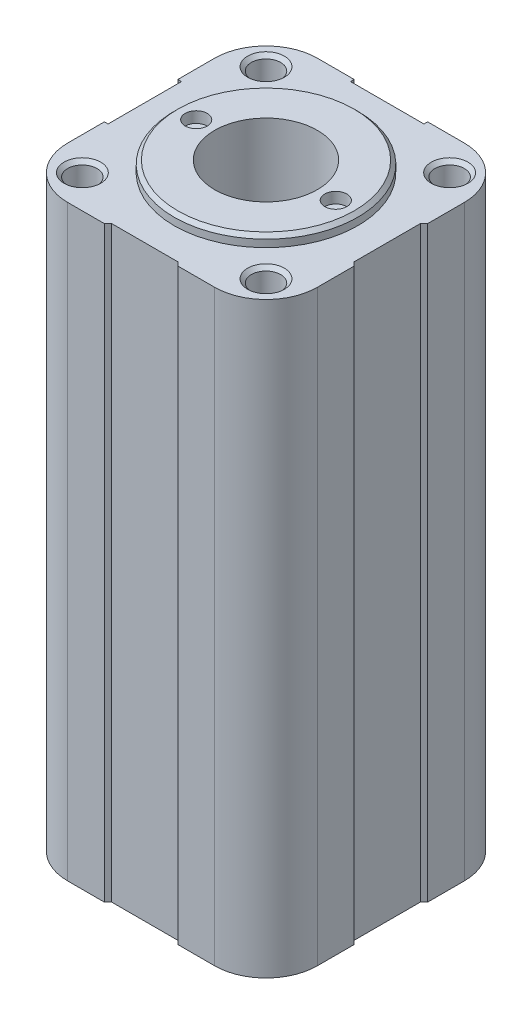
SolidWorks part; units mm, degrees
material "ｽﾃﾝﾚｽ鋼(ｸﾛﾑ)"
ref_plane "正面" through (0, 0, 0) normal (0, 0, 1) x (1, 0, 0)
ref_plane "平面" through (0, 0, 0) normal (0, 1, 0) x (1, 0, 0)
ref_plane "右側面" through (0, 0, 0) normal (1, 0, 0) x (0, 0, -1)
sketch "ｽｹｯﾁ1" plane through (0, 0, 0) normal (0, 1, 0) x (1, 0, 0)
  line L0 (-17, 17) -> (17, 17)
  line L1 (-17, 17) -> (-17, -17)
  line L2 (17, 17) -> (17, -17)
  line L3 (-17, -17) -> (17, -17)
  line L4 (-17, 17) -> (17, -17) construction
  line L5 (17, 17) -> (-17, -17) construction
  point P1 (0, 0)
extrude "ﾎﾞｽ - 押し出し1" add sketch "ｽｹｯﾁ1" along normal blind 80
fillet "ﾌｨﾚｯﾄ1" radius 7 4 edges at (17, 40, -17) (-17, 40, -17) (-17, 40, 17) (17, 40, 17)
sketch "ｽｹｯﾁ10" plane through (0, 0, 0) normal (0, -1, 0) x (1, 0, 0)
  line L1 (-5, -17) -> (5, -17)
  line L2 (-5, -17) -> (-5, -16.5)
  line L3 (-5, -16.5) -> (5, -16.5)
  line L4 (5, -17) -> (5, -16.5)
extrude "ｶｯﾄ - 押し出し8" cut sketch "ｽｹｯﾁ13" against normal up to next
sketch "ｽｹｯﾁ13" plane through (0, 0, 0) normal (0, -1, 0) x (1, 0, 0)
  line L1 (-5, 17) -> (5, 17)
  line L2 (-5, 17) -> (-5, 16.5)
  line L3 (-5, 16.5) -> (5, 16.5)
  line L4 (5, 17) -> (5, 16.5)
  line L5 (-17, -5) -> (-16.5, -5)
  line L6 (-17, -5) -> (-17, 5)
  line L7 (-17, 5) -> (-16.5, 5)
  line L8 (-16.5, -5) -> (-16.5, 5)
  line L9 (-5, -17) -> (5, -17)
  line L10 (-5, -17) -> (-5, -16.5)
  line L11 (-5, -16.5) -> (5, -16.5)
  line L12 (5, -17) -> (5, -16.5)
  line L13 (17, -5) -> (16.5, -5)
  line L14 (17, -5) -> (17, 5)
  line L15 (17, 5) -> (16.5, 5)
  line L16 (16.5, -5) -> (16.5, 5)
chamfer "面取り1" distance 0.5 angle 45 8 edges at (-5, 40, 16.5) (5, 40, 16.5) (16.5, 40, 5) (16.5, 40, -5) (5, 40, -16.5) (-5, 40, -16.5) (-16.5, 40, -5) (-16.5, 40, 5)
sketch "ｽｹｯﾁ18" plane through (0, 0, 0) normal (0, -1, 0) x (1, 0, 0)
  circle A0 centre (12.5, -12.5) radius 2
  circle A1 centre (-12.5, 12.5) radius 2
extrude "ｶｯﾄ - 押し出し9" cut sketch "ｽｹｯﾁ18" against normal blind 7.2
chamfer "面取り2" distance 0.5 angle 45 2 edges at (-12.5, 0, 10.5) (12.5, 0, -14.5)
sketch "ｽｹｯﾁ19" plane through (0, 80, 0) normal (0, 1, 0) x (1, 0, 0)
  circle A0 centre (-12.5, -12.5) radius 2
  circle A1 centre (-12.5, 12.5) radius 2
  circle A2 centre (12.5, 12.5) radius 2
  circle A3 centre (12.5, -12.5) radius 2
  point P11 (0, 0)
  dimension "D1" = 4
extrude "ｶｯﾄ - 押し出し10" cut sketch "ｽｹｯﾁ19" against normal blind 7.2
chamfer "面取り3" distance 0.5 angle 45 4 edges at (12.5, 80, -10.5) (12.5, 80, 14.5) (-12.5, 80, 14.5) (-12.5, 80, -10.5)
sketch "ｽｹｯﾁ20" plane through (0, 80, 0) normal (0, 1, 0) x (1, 0, 0)
  circle A0 centre (0, 0) radius 12.5
extrude "ﾎﾞｽ - 押し出し2" add sketch "ｽｹｯﾁ20" along normal blind 1.5
chamfer "面取り4" distance 0.5 angle 45 1 edges at (0, 81.5, 12.5)
sketch "ｽｹｯﾁ21" plane through (0, 81.5, 0) normal (0, 1, 0) x (1, 0, 0)
  circle A0 centre (0, 0) radius 7
  circle A1 centre (9.5, 0) radius 1.5
  circle A2 centre (-9.5, 0) radius 1.5
  point P10 (0, 0)
  dimension "D1" = 2
extrude "ｶｯﾄ - 押し出し11" cut sketch "ｽｹｯﾁ21" against normal blind 1.5
sketch "ｽｹｯﾁ23" plane through (0, 80, 0) normal (0, 1, 0) x (1, 0, 0)
  circle A0 centre (0, 0) radius 7
extrude "ｶｯﾄ - 押し出し12" cut sketch "ｽｹｯﾁ23" against normal blind 13.5
extrude "ｶｯﾄ - 押し出し4" cut sketch "ｽｹｯﾁ10" against normal up to next
sketch "ｽｹｯﾁ12" plane through (0, 0, 0) normal (0, -1, 0) x (1, 0, 0)
  line L1 (-17, -5) -> (-16.5, -5)
  line L2 (-17, -5) -> (-17, 5)
  line L3 (-17, 5) -> (-16.5, 5)
  line L4 (-16.5, -5) -> (-16.5, 5)
extrude "ｶｯﾄ - 押し出し5" cut sketch "ｽｹｯﾁ12" against normal up to next
